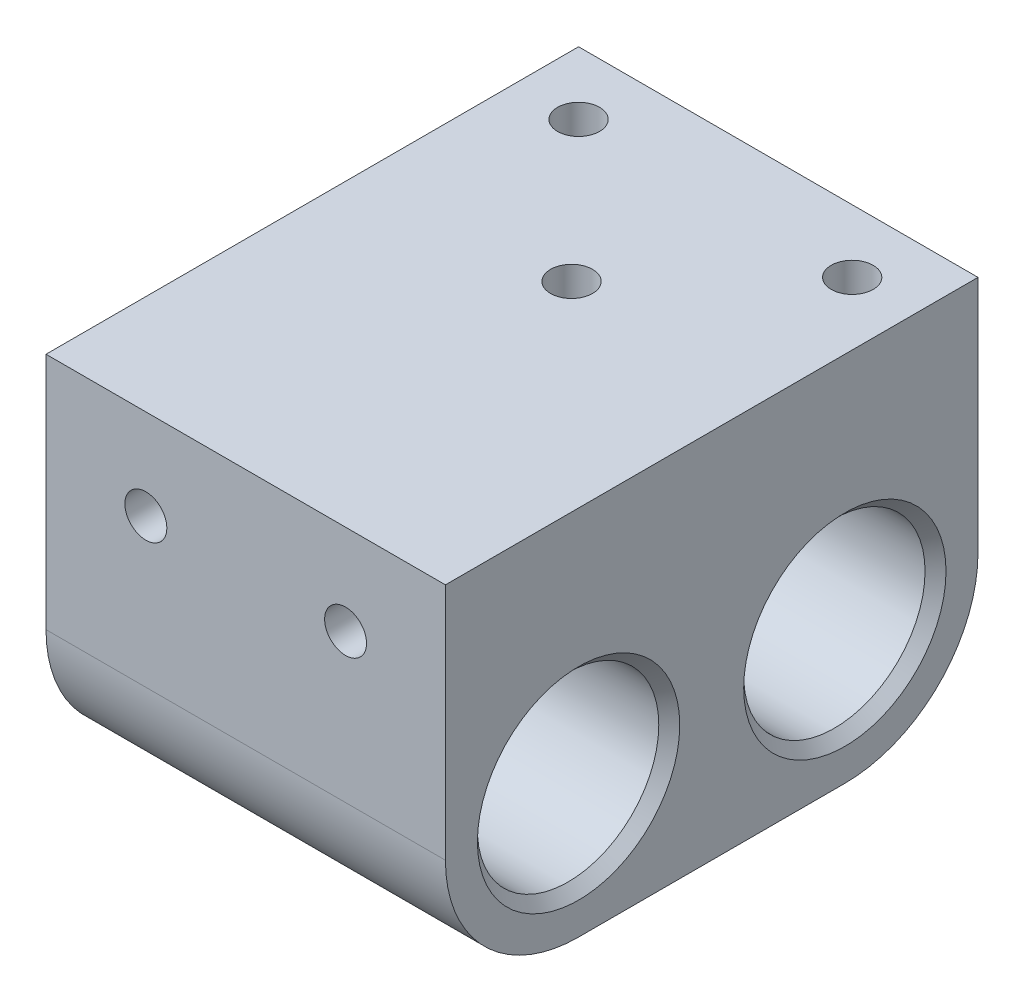
SolidWorks part; units mm, degrees
ref_plane "Front Plane" through (0, 0, 0) normal (0, 0, 1) x (1, 0, 0)
ref_plane "Top Plane" through (0, 0, 0) normal (0, 1, 0) x (1, 0, 0)
ref_plane "Right Plane" through (0, 0, 0) normal (1, 0, 0) x (0, 0, -1)
sketch "Sketch1" plane through (0, 0, 0) normal (1, 0, 0) x (0, 0, -1)
  line L0 (25.4, 22.75) -> (25.4, 0) construction
  line L1 (0, 22.75) -> (50.8, 22.75)
  line L2 (0, 22.75) -> (0, 0)
  line L3 (0, 0) -> (50.8, 0)
  line L4 (50.8, 22.75) -> (50.8, 0)
  circle A0 centre (12.7, 0) radius 8.65
  circle A1 centre (38.1, 0) radius 8.65
  circle A2 centre (12.7, 0) radius 12.7
  circle A3 centre (38.1, 0) radius 12.7
  dimension "D1" = 17.3
  dimension "D6" = 25.4
  dimension "D2" = 25.4
  dimension "D3" = 50.8
  dimension "D4" = 12.7
  dimension "D5" = 22.75
extrude "Boss-Extrude2" add sketch "Sketch1" along normal blind 38.1 contours L3 A2 A0 | L3 A2 A0 | L3 A3 A1 | L3 A3 A1 | L1 L0 L3 A3 L4 | L0 L1 L2 L3 A2 region at (0, 16.0478, -25.4) region at (0, 12.416, -12.7) region at (0, -0.284, -2.025) region at (0, -12.416, -38.1) region at (0, 0.284, -48.775)
sketch "Sketch5" plane through (0, 22.75, 0) normal (0, 1, 0) x (1, 0, 0)
  line L11 (0, 0) -> (38.1, 0)
  line L12 (0, 0) -> (0, 50.8)
  line L19 (0, 50.8) -> (38.1, 50.8)
  line L24 (38.1, 0) -> (38.1, 50.8)
ref_plane "Plane1" through (0, -12.7, 0) normal (0, -1, 0) x (-1, 0, 0)
sketch "Sketch6" plane through (0, -12.7, 0) normal (0, -1, 0) x (-1, 0, 0)
  line L0 (-38.1, 38.1) -> (0, 38.1)
  line L1 (-38.1, 50.8) -> (-38.1, 25.4) construction
  line L2 (0, 25.4) -> (0, 50.8) construction
  line L3 (-38.1, 12.7) -> (0, 12.7)
  line L4 (-38.1, 25.4) -> (-38.1, 0) construction
  line L5 (0, 0) -> (0, 25.4) construction
  line L7 (-38.1, 38.1) -> (0, 38.1)
  line L8 (-38.1, 38.1) -> (-38.1, 12.7)
  line L9 (-38.1, 12.7) -> (0, 12.7)
  line L10 (0, 38.1) -> (0, 12.7)
  circle A0 centre (-19.05, 38.1) radius 2
  circle A1 centre (-19.05, 12.7) radius 2
  dimension "D1" = 4
extrude "Cut-Extrude5" cut sketch "Sketch6" against normal up to next contours A0 | A1
extrude "Boss-Extrude3" add sketch "Sketch6<3>" against normal up to next contours A1 L3 L10 L0 A0 L8 region at (19.05, -12.7, -25.4)
sketch "Sketch6<3>" plane through (0, -12.7, 0) normal (0, -1, 0) x (-1, 0, 0) same geometry as "Sketch6"
sketch "Sketch10" plane through (0, 0, 0) normal (0, 0, 1) x (1, 0, 0)
  line L0 (38.1, 22.75) -> (38.1, 0) construction
  line L1 (0, 22.75) -> (38.1, 22.75)
  line L2 (0, 22.75) -> (0, 5.5563)
  line L3 (0, 5.5563) -> (38.1, 5.5563)
  line L4 (38.1, 22.75) -> (38.1, 5.5563)
  line L5 (19.05, 22.75) -> (19.05, 5.5563) construction
  line L6 (0, 14.1531) -> (19.05, 14.1531) construction
  line L7 (19.05, 14.1531) -> (38.1, 14.1531) construction
  circle A0 centre (9.525, 14.1531) radius 2
  circle A1 centre (28.575, 14.1531) radius 2
  dimension "D2" = 4
  dimension "D1" = 17.1937
extrude "Cut-Extrude6" cut sketch "Sketch10" against normal blind 8 contours A0 | A1 region at (9.525, 14.1531, 0) region at (28.575, 14.1531, 0)
sketch "Sketch11" plane through (0, 22.75, 0) normal (0, 1, 0) x (1, 0, 0)
  line L0 (0, 25.4) -> (38.1, 25.4) construction
  line L1 (0, 0) -> (0, 50.8) construction
  line L2 (38.1, 0) -> (38.1, 50.8) construction
  line L3 (0, 36.76) -> (38.1, 36.76)
  line L4 (19.05, 36.76) -> (19.05, 25.4) construction
  line L6 (0, 36.76) -> (0, 50.8)
  line L7 (38.1, 36.76) -> (38.1, 50.8)
  line L9 (19.05, 36.76) -> (19.05, 50.8) construction
  line L10 (38.1, 50.8) -> (0, 50.8) construction
  circle A0 centre (19.05, 31.08) radius 2
  circle A1 centre (6, 44.8) radius 2
  circle A2 centre (32.1, 44.8) radius 2
  dimension "D2" = 4
  dimension "D4" = 4
  dimension "D1" = 11.36
  dimension "D3" = 6
  dimension "D5" = 6
extrude "Cut-Extrude7" cut sketch "Sketch11" against normal blind 8 contours A1 | A2 | A0 region at (6, 22.75, -44.8) region at (32.1, 22.75, -44.8)
chamfer "Chamfer1" distance 1 angle 45 4 edges at (38.1, 0, -21.35) (38.1, 0, -46.75) (0, 0, -21.35) (0, 0, -46.75)
equation "\"Ø Smaller Shaft\"=6.35"
equation "\"Shaft Distance\"= 25.4"
equation "\"Width\"= \"Ø Smaller Shaft\" * 2 + \"Shaft Distance\" + \"Width End\" * 2"
equation "\"Width End\"= 6.35"
equation "\"Length\"= 38.1"
equation "\"Rod to Belt\"= 31.75 + 3"
equation "\"Nom Tolerance\"= 0.15"
equation "\"D1@Sketch1\"=\"Ø Graphite Holder\" + \"Nom Tolerance\"*2"
equation "\"D2@Sketch1\"=\"Shaft Distance\""
equation "\"D3@Sketch1\"= \"Width\""
equation "\"D4@Sketch1\"=\"Shaft Distance\"/2"
equation "\"Belt\"= 6"
equation "\"Belt Thickness\"=1.38"
equation "\"Ø Pulley\"= 10.9"
equation "\"Pully Distance\"= 35"
equation "\"D6@Sketch1\"=\"Ø Smaller Shaft\"*4"
equation "\"D5@Sketch1\"=\"Rod to Belt\"+(\"Belt\"/2)-15"
equation "\"D1@Boss-Extrude2\"=\"Length\""
equation "\"Ø Outer Washer\"=12.7"
equation "\"Washer Thickness\"=2"
equation "\"D1@Cut-Extrude2\"=\"Washer Thickness\""
equation "\"M3 Heated Insert Hole\"= 4"
equation "\"D1@Sketch6\"=\"M3 Heated Insert Hole\""
equation "\"D1@Sketch10\"=\"Rod to Belt\"+(\"Belt\"/2)-15-(\"Ø Smaller Shaft\"*1.75)/2"
equation "\"D2@Sketch10\"=\"M3 Heated Insert Hole\""
equation "\"D1@Sketch11\"=(\"Pully Distance\"/2)-(\"Ø Pulley\"/2)-(\"Belt Thickness\"/2)"
equation "\"Ø Graphite Holder\"= 17"
equation "\"D2@Sketch11\"=\"M3 Heated Insert Hole\""
equation "\"D4@Sketch11\"=\"M3 Heated Insert Hole\""
